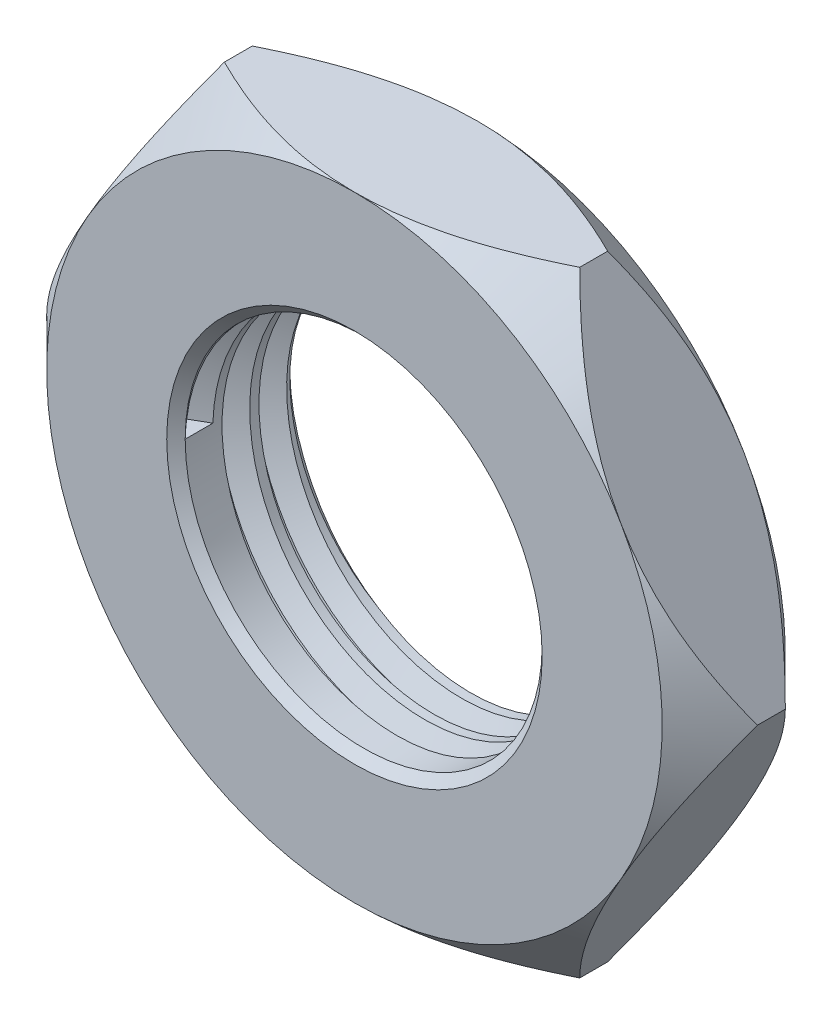
SolidWorks part; units mm, degrees
ref_plane "Front Plane" through (0, 0, 0) normal (0, 0, 1) x (1, 0, 0)
ref_plane "Top Plane" through (0, 0, 0) normal (0, 1, 0) x (1, 0, 0)
ref_plane "Right Plane" through (0, 0, 0) normal (1, 0, 0) x (0, 0, -1)
sketch "Sketch1" plane through (0, 0, 0) normal (0, 0, 1) x (1, 0, 0)
  line L1 (57.735, 0) -> (28.8675, 50)
  line L2 (28.8675, 50) -> (-28.8675, 50)
  line L3 (-28.8675, 50) -> (-57.735, 0)
  line L4 (-57.735, 0) -> (-28.8675, -50)
  line L5 (-28.8675, -50) -> (28.8675, -50)
  line L6 (28.8675, -50) -> (57.735, 0)
  circle A0 centre (0, 0) radius 50 construction
extrude "Boss-Extrude1" add sketch "Sketch1" along normal mid plane 20
sketch "Sketch2" plane through (0, 0, 10) normal (0, 0, 1) x (1, 0, 0)
  circle A0 centre (0, 0) radius 50
extrude "Cut-Extrude1" cut sketch "Sketch2" against normal blind 20 draft 45 flip side to cut
mirror "Mirror1" about plane through (0, 0, 0) normal (0, 0, 1) of "Cut-Extrude1"
sketch "Sketch3" plane through (0, 0, 10) normal (0, 0, 1) x (1, 0, 0)
  circle A0 centre (0, 0) radius 29
extrude "Cut-Extrude2" cut sketch "Sketch3" against normal through all
chamfer "Chamfer1" distance 1.5 angle 45 1 edges at (29, 0, -10)
chamfer "Chamfer2" distance 1.5 angle 45 1 edges at (29, 0, 10)
thread "Thread1" pitch 6 method cut profile "Thread Profile2" start angle 0, offset 0, length 0, pitch 6, diameter 58
ref_plane "Plane2" through (-29, 0, 8.5) normal (0, -1, 0) x (-1, 0, 0)
sketch "Thread Profile2" plane through (-29, 0, 8.5) normal (0, -1, 0) x (-1, 0, 0)
  line L0 (0, 0) -> (0, 6) construction
  line L1 (0, 0) -> (3.2476, 1.875)
  line L2 (3.2476, 1.875) -> (3.2476, 2.625)
  line L3 (3.2476, 2.625) -> (0, 4.5)
  line L4 (3.2476, 2.25) -> (0, 2.25) construction
  line L11 (0, 0) -> (0, 4.5)
  point P2 (0, 0)
  dimension "Pitch" = 6
  dimension "Profile_Angle" = 60
  dimension "Profile_Land" = 0.75
  dimension "Profile_Height" = 3.2476
